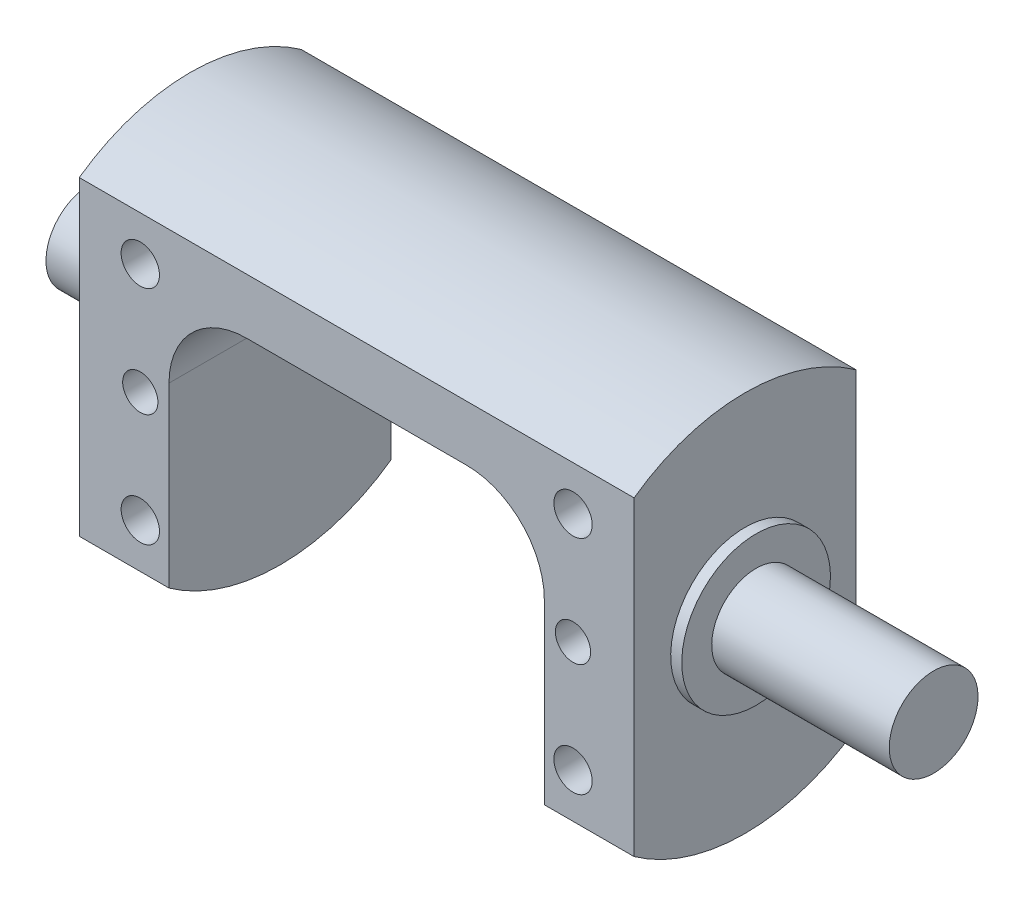
SolidWorks part; units mm, degrees
material "AISI 316 Annealed Stainless Steel Bar (SS)"
ref_plane "Front Plane" through (0, 0, 0) normal (0, 0, 1) x (1, 0, 0)
ref_plane "Top Plane" through (0, 0, 0) normal (0, 1, 0) x (1, 0, 0)
ref_plane "Right Plane" through (0, 0, 0) normal (1, 0, 0) x (0, 0, -1)
sketch "Sketch1" plane through (0, 0, 0) normal (1, 0, 0) x (0, 0, -1)
  line L0 (0, 17.2047) -> (0, 0)
  line L1 (-10, -14) -> (10, -14)
  line L2 (-10, -14) -> (-10, 14)
  line L3 (-10, 14) -> (10, 14)
  line L4 (10, -14) -> (10, 14)
  line L5 (-10, -14) -> (10, 14) construction
  line L6 (-10, 14) -> (10, -14) construction
  circle A0 centre (0, 0) radius 17.2047
  dimension "D1" = 20
  dimension "D2" = 28
sketch "Sketch2" plane through (0, 0, 0) normal (0, 0, 1) x (1, 0, 0)
  line L0 (-34, 0) -> (42, 0)
  line L1 (42, 0) -> (42, 4)
  line L2 (42, 4) -> (26, 4)
  line L3 (25, 6.7) -> (25, 17.2047)
  line L4 (25, 17.2047) -> (-25, 17.2047)
  line L5 (-25, 17.2047) -> (-25, 6.7)
  line L6 (-27.5, 4) -> (-34, 4)
  line L7 (-34, 4) -> (-34, 0)
  line L10 (26, 4) -> (26, 6.7)
  line L11 (26, 6.7) -> (25, 6.7)
  line L12 (-25, 6.7) -> (-27.5, 6.7)
  line L13 (-27.5, 6.7) -> (-27.5, 4)
  dimension "D1" = 4
  dimension "D2" = 2.5
  dimension "D3" = 42
  dimension "D4" = 50
  dimension "D5" = 6.7
  dimension "D6" = 9
  dimension "D7" = 1
revolve "Revolve1" add sketch "Sketch2" angle 360 about L0
sketch "Sketch3" plane through (-25, 0, 0) normal (-1, 0, 0) x (0, 0, 1)
  line L2 (10, -14) -> (10, 14) construction
  line L3 (-10, 17.2047) -> (10, 17.2047)
  line L4 (-10, 17.2047) -> (-10, -17.2047)
  line L5 (-10, -17.2047) -> (10, -17.2047)
  line L6 (10, 17.2047) -> (10, -17.2047)
  line L7 (-10, -14) -> (-10, 14) construction
  circle A0 centre (0, 0) radius 17.2047 construction
extrude "Cut-Extrude1" cut sketch "Sketch3" against normal through all both and the other way through all flip side to cut
hole_wizard "#8-32 Tapped Hole1" positions "Sketch4" profile "Sketch5" tap size "#8-32" standard "ANSI Inch"
sketch "Sketch4" plane through (0, 0, -10) normal (0, 0, -1) x (-1, 0, 0)
  line L1 (-19.5, 10) -> (19.5, 10)
  line L2 (-19.5, 10) -> (-19.5, -10)
  line L3 (-19.5, -10) -> (19.5, -10)
  line L4 (19.5, 10) -> (19.5, -10)
  line L6 (-25, 14) -> (-25, -14) construction
  line L7 (-19.5, 0) -> (0, 0) construction
  line L8 (0, 0) -> (0, 10) construction
  point P1 (-19.5, 10)
  point P2 (19.5, -10)
  point P53 (-19.5, -10)
  point P54 (19.5, 10)
  dimension "D1" = 5.5
  dimension "D2" = 20
sketch "Sketch5" plane through (19.5, 10, -10) normal (1, 0, 0) x (0, 1, 0)
  line L0 (0, 0) -> (0, 11.7478)
  line L1 (0, 11.7478) -> (1.7272, 10.71)
  line L2 (1.7272, 10.71) -> (1.7272, 0)
  line L5 (1.7272, 0) -> (0, 0)
  line L10 (0, 11.7478) -> (-1.7272, 10.71) construction
  line L11 (0, -6.35) -> (0, 107.95) construction
  dimension "Tap Drill Dia." = 3.4544
  dimension "Tap Drill Depth" = 10.71
  dimension "Drill Angle" = 118
cosmetic thread "Hole Thread1" parameters "D1"=8.33, "D2"=4.1656
cosmetic thread "Hole Thread2" parameters "D1"=8.33, "D2"=4.1656
cosmetic thread "Hole Thread3" parameters "D1"=8.33, "D2"=4.1656
cosmetic thread "Hole Thread4" parameters "D1"=8.33, "D2"=4.1656
hole_wizard "1/8 (0.1250) Dowel Hole1" positions "Sketch6" profile "Sketch7" hole size "1/8" standard "ANSI Inch"
sketch "Sketch6" plane through (0, 0, -10) normal (0, 0, -1) x (-1, 0, 0)
  line L0 (-19.5, 10) -> (-19.5, -10) construction
  line L1 (19.5, 10) -> (19.5, -10) construction
  point P0 (-19.5, 0)
  point P2 (19.5, 0)
sketch "Sketch7" plane through (19.5, 0, -10) normal (1, 0, 0) x (0, 1, 0)
  line L0 (0, 0) -> (0, 6.9539)
  line L1 (0, 6.9539) -> (1.5875, 6)
  line L2 (1.5875, 6) -> (1.5875, 0)
  line L5 (1.5875, 0) -> (0, 0)
  line L10 (0, 6.9539) -> (-1.5875, 6) construction
  line L11 (0, -6.35) -> (0, 107.95) construction
  dimension "Hole Dia." = 3.175
  dimension "Hole Depth" = 6
  dimension "Drill Angle" = 118
mirror "Mirror1" about plane through (0, 0, 0) normal (0, 0, 1) of "1/8 (0.1250) Dowel Hole1", "#8-32 Tapped Hole1"
cosmetic thread "Hole Thread5" parameters "D1"=8.33, "D2"=4.1656
cosmetic thread "Hole Thread6" parameters "D1"=8.33, "D2"=4.1656
cosmetic thread "Hole Thread7" parameters "D1"=8.33, "D2"=4.1656
cosmetic thread "Hole Thread8" parameters "D1"=8.33, "D2"=4.1656
hole_wizard "#8-32 Tapped Hole2" positions "Sketch8" profile "Sketch10" tap size "#8-32" standard "ANSI Inch"
sketch "Sketch8" plane through (-34, 0, 0) normal (-1, 0, 0) x (0, 0, 1)
  point P0 (0, 0)
sketch "Sketch10" plane through (-34, 0, 0) normal (0, 1, 0) x (0, 0, 1)
  line L0 (0, 0) -> (0, 11.7478)
  line L1 (0, 11.7478) -> (1.7272, 10.71)
  line L2 (1.7272, 10.71) -> (1.7272, 0)
  line L5 (1.7272, 0) -> (0, 0)
  line L10 (0, 11.7478) -> (-1.7272, 10.71) construction
  line L11 (0, -6.35) -> (0, 107.95) construction
  dimension "Tap Drill Dia." = 3.4544
  dimension "Tap Drill Depth" = 10.71
  dimension "Drill Angle" = 118
cosmetic thread "Hole Thread9" parameters "D1"=8.33, "D2"=4.1656
sketch "Sketch11" plane through (0, 0, 10) normal (0, 0, 1) x (1, 0, 0)
  line L0 (25, 14) -> (-25, 14) construction
  line L1 (-4.7728, 14) -> (4.7728, 14)
  line L2 (-14.7728, 4) -> (-14.7728, -4)
  line L3 (-4.7728, -14) -> (4.7728, -14)
  line L4 (14.7728, 4) -> (14.7728, -4)
  line L5 (-25, -14) -> (25, -14) construction
  line L6 (0, 0) -> (0, 14) construction
  circle A0 centre (-19.5, 10) radius 1.7272 construction
  arc A1 (4.7728, -14) -> (14.7728, -4) centre (4.7728, -4) ccw
  arc A2 (-14.7728, -4) -> (-4.7728, -14) centre (-4.7728, -4) ccw
  arc A3 (4.7728, 14) -> (14.7728, 4) centre (4.7728, 4) cw
  arc A4 (-4.7728, 14) -> (-14.7728, 4) centre (-4.7728, 4) ccw
  point P15 (14.7728, -14)
  point P22 (-14.7728, 14)
  dimension "D1" = 3
  dimension "D2" = 10
extrude "Cut-Extrude2" [suppressed] cut sketch "Sketch11" against normal through all
sketch "Sketch12" plane through (0, 0, 10) normal (0, 0, 1) x (1, 0, 0)
  line L0 (25, 14) -> (-25, 14) construction
  line L1 (-9.9125, -37.3916) -> (9.9125, -37.3916)
  line L2 (-16.9125, -30.3916) -> (-16.9125, 2)
  line L3 (-9.9125, 9) -> (9.9125, 9)
  line L4 (16.9125, -30.3916) -> (16.9125, 2)
  line L5 (-16.9125, -37.3916) -> (16.9125, 9) construction
  line L6 (-16.9125, 9) -> (16.9125, -37.3916) construction
  line L7 (0, 14) -> (0, -14.1958) construction
  circle A1 centre (19.5, 0) radius 1.5875 construction
  arc A2 (-9.9125, -37.3916) -> (-16.9125, -30.3916) centre (-9.9125, -30.3916) cw
  arc A3 (9.9125, -37.3916) -> (16.9125, -30.3916) centre (9.9125, -30.3916) ccw
  arc A4 (9.9125, 9) -> (16.9125, 2) centre (9.9125, 2) cw
  arc A5 (-16.9125, 2) -> (-9.9125, 9) centre (-9.9125, 2) cw
  point P0 (0, -14.1958)
  dimension "D3" = 7
  dimension "D1" = 5
  dimension "D2" = 1
extrude "Cut-Extrude3" cut sketch "Sketch12" against normal through all both and the other way through all
